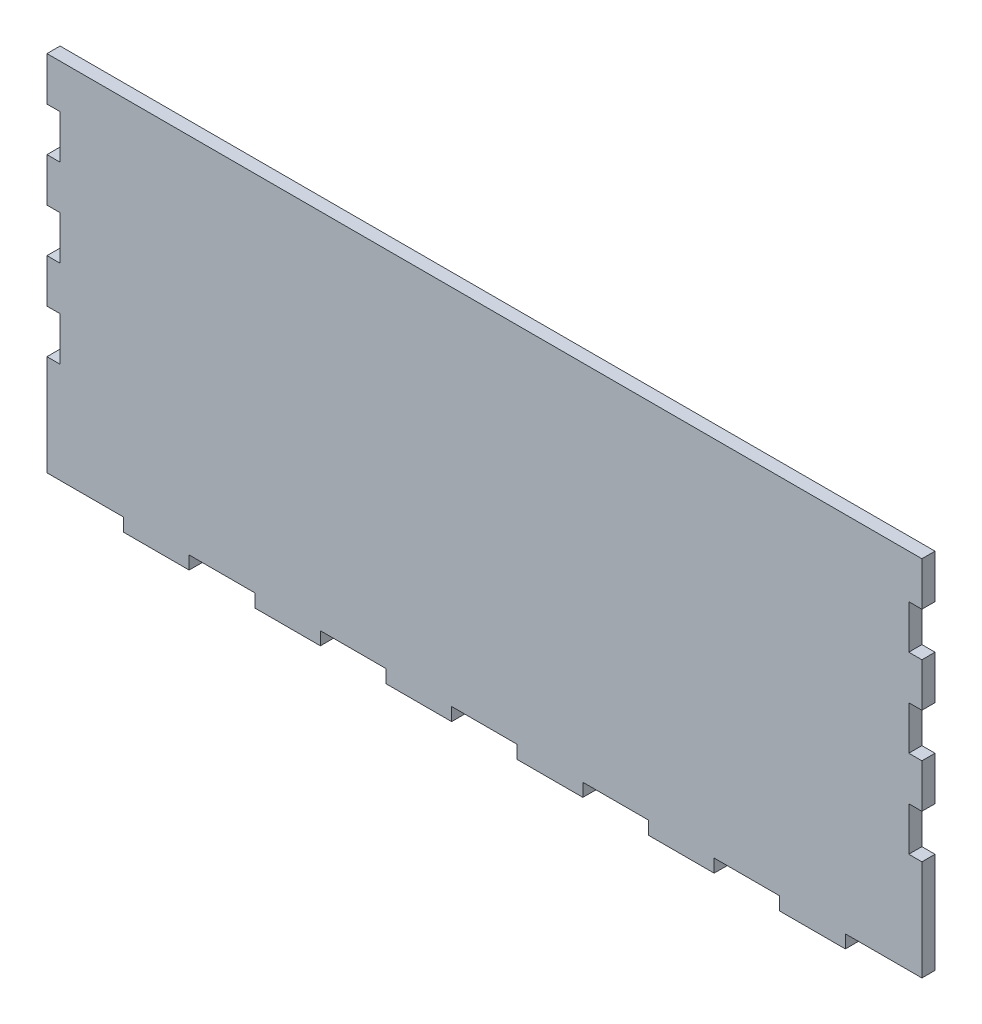
SolidWorks part; units mm, degrees
ref_plane "Front Plane" through (0, 0, 0) normal (0, 0, 1) x (1, 0, 0)
ref_plane "Top Plane" through (0, 0, 0) normal (0, 1, 0) x (1, 0, 0)
ref_plane "Right Plane" through (0, 0, 0) normal (1, 0, 0) x (0, 0, -1)
sketch "Sketch1" plane through (0, 0, 0) normal (0, 0, 1) x (1, 0, 0)
  line L0 (-97, 0) -> (97, 0) construction
  line L1 (0, -25.5) -> (0, 57.5) construction
  line L2 (100, -2.5) -> (97, -2.5)
  line L3 (-97, 57.5) -> (97, 57.5)
  line L4 (100, -25.5) -> (100, -2.5)
  line L5 (0, -25.5) -> (7.5, -25.5)
  line L6 (-97, -25.5) -> (-100, -25.5)
  line L7 (-100, -25.5) -> (-100, -2.5)
  line L8 (-97, 57.5) -> (-100, 57.5)
  line L9 (-100, 57.5) -> (-100, 47.5)
  line L10 (-100, 47.5) -> (-97, 47.5)
  line L11 (-97, 47.5) -> (-97, 37.5)
  line L12 (-97, 37.5) -> (-100, 37.5)
  line L13 (-100, 37.5) -> (-100, 27.5)
  line L14 (100, 17.5) -> (100, 7.5)
  line L15 (-100, 27.5) -> (-97, 27.5)
  line L16 (-97, 27.5) -> (-97, 17.5)
  line L17 (97, 7.5) -> (100, 7.5)
  line L18 (97, 17.5) -> (100, 17.5)
  line L19 (97, 7.5) -> (97, -2.5)
  line L20 (97, 27.5) -> (97, 17.5)
  line L21 (100, 27.5) -> (97, 27.5)
  line L22 (100, 37.5) -> (100, 27.5)
  line L23 (97, 37.5) -> (100, 37.5)
  line L24 (97, 47.5) -> (97, 37.5)
  line L25 (100, 47.5) -> (97, 47.5)
  line L26 (100, 57.5) -> (100, 47.5)
  line L27 (97, 57.5) -> (100, 57.5)
  line L28 (7.5, -25.5) -> (7.5, -28.5)
  line L29 (7.5, -28.5) -> (22.5, -28.5)
  line L30 (22.5, -28.5) -> (22.5, -25.5)
  line L31 (30, -25.5) -> (37.5, -25.5)
  line L32 (37.5, -25.5) -> (37.5, -28.5)
  line L33 (37.5, -28.5) -> (52.5, -28.5)
  line L34 (52.5, -28.5) -> (52.5, -25.5)
  line L35 (60, -25.5) -> (67.5, -25.5)
  line L36 (67.5, -25.5) -> (67.5, -28.5)
  line L37 (67.5, -28.5) -> (82.5, -28.5)
  line L38 (82.5, -28.5) -> (82.5, -25.5)
  line L39 (22.5, -25.5) -> (30, -25.5)
  line L40 (52.5, -25.5) -> (60, -25.5)
  line L41 (82.5, -25.5) -> (97, -25.5)
  line L42 (0, -25.5) -> (-7.5, -25.5)
  line L43 (-7.5, -25.5) -> (-7.5, -28.5)
  line L44 (-7.5, -28.5) -> (-22.5, -28.5)
  line L45 (-22.5, -28.5) -> (-22.5, -25.5)
  line L46 (-22.5, -25.5) -> (-37.5, -25.5)
  line L47 (-37.5, -25.5) -> (-37.5, -28.5)
  line L48 (-37.5, -28.5) -> (-52.5, -28.5)
  line L49 (-52.5, -28.5) -> (-52.5, -25.5)
  line L50 (-52.5, -25.5) -> (-67.5, -25.5)
  line L51 (-67.5, -25.5) -> (-67.5, -28.5)
  line L52 (-100, -2.5) -> (-97, -2.5)
  line L53 (97, -25.5) -> (100, -25.5)
  line L56 (-97, 7.5) -> (-97, -2.5)
  line L57 (-97, 17.5) -> (-100, 17.5)
  line L58 (-97, 7.5) -> (-100, 7.5)
  line L59 (-100, 17.5) -> (-100, 7.5)
  line L60 (-67.5, -28.5) -> (-82.5, -28.5)
  line L62 (-82.5, -28.5) -> (-82.5, -25.5)
  line L63 (-82.5, -25.5) -> (-97, -25.5)
  dimension "D2" = 7.5
  dimension "D4" = 83
  dimension "D5" = 10
  dimension "D6" = 194
  dimension "D8" = 7.5
  dimension "D9" = 15
  dimension "D10" = 3
  dimension "D11" = 10
  dimension "D7" = 10
  dimension "D13" = 10
  dimension "D12" = 10
  dimension "D14" = 7.5
  dimension "D15" = 14.5
  dimension "D16" = 10
  dimension "D18" = 3
  dimension "D19" = 15
  dimension "D20" = 15
  dimension "D21" = 15
  dimension "D22" = 15
  dimension "D23" = 15
extrude "Boss-Extrude1" add sketch "Sketch1" along normal blind 3
